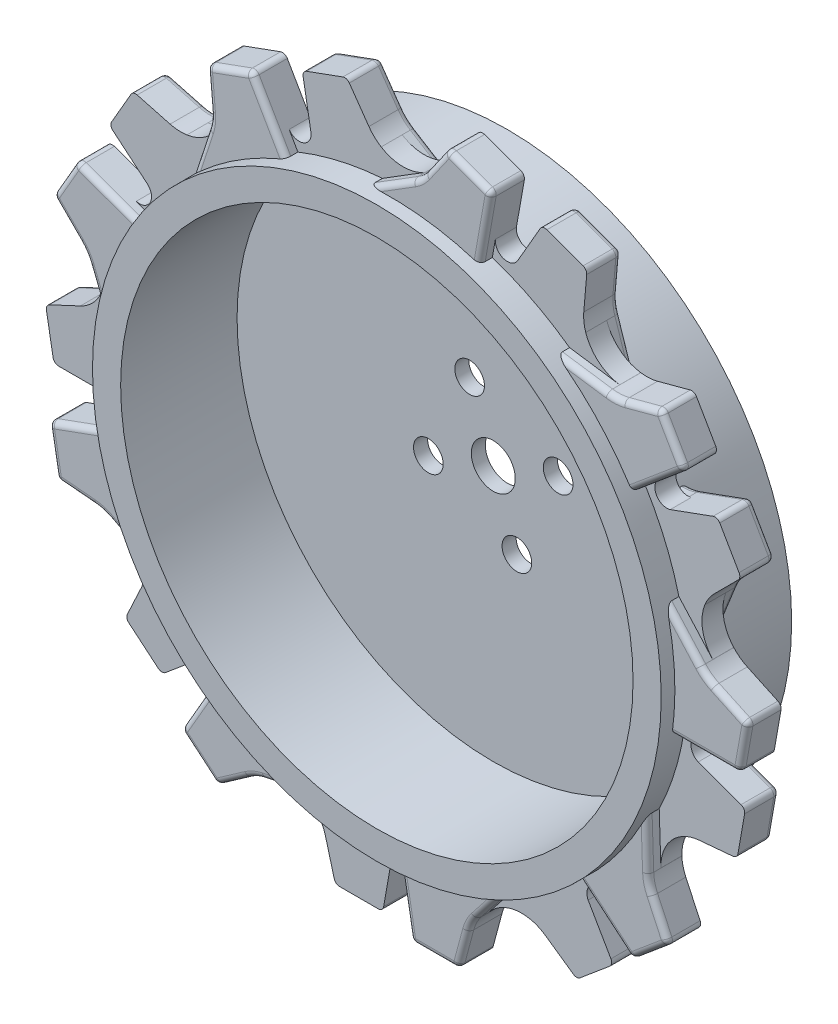
SolidWorks part; units mm, degrees
ref_plane "Front Plane" through (0, 0, 0) normal (0, 0, 1) x (1, 0, 0)
ref_plane "Top Plane" through (0, 0, 0) normal (0, 1, 0) x (1, 0, 0)
ref_plane "Right Plane" through (0, 0, 0) normal (1, 0, 0) x (0, 0, -1)
sketch "Sketch1" plane through (0, 0, 0) normal (0, 0, 1) x (1, 0, 0)
  line L0 (0, 45.1139) -> (0, -45.1139) construction
  line L1 (38.9794, 0) -> (-38.9794, 0) construction
  line L2 (2.4045, 32.578) -> (-2.5355, 35.6448)
  line L3 (-3.9413, 36.9734) -> (-6.1886, 40.1749)
  line L4 (-6.9314, 40.4086) -> (-11.0919, 38.8936)
  line L5 (-11.5032, 38.1809) -> (-10.5355, 32.7)
  line L6 (15.7303, 36.6424) -> (12.9485, 31.8217)
  line L7 (20.6644, 35.4101) -> (16.5034, 36.924)
  line L8 (20.7468, 30.8567) -> (21.0832, 34.7537)
  line L9 (22.7827, 23.4107) -> (20.9697, 28.9353)
  line L10 (35.6034, 17.9585) -> (30.3737, 16.0537)
  line L11 (38.591, 13.8429) -> (36.3766, 17.6772)
  line L12 (35.7273, 10.3018) -> (38.4899, 13.0708)
  line L13 (32.5006, 3.2892) -> (34.663, 8.6867)
  line L14 (38.8173, -9.1284) -> (33.5868, -7.226)
  line L15 (38.4605, -14.2015) -> (39.2288, -9.8409)
  line L16 (33.9906, -15.0734) -> (37.8867, -14.728)
  line L17 (27.0112, -18.3714) -> (32.1371, -15.6266)
  line L18 (23.8682, -31.944) -> (21.0842, -27.1246)
  line L19 (20.3339, -35.601) -> (23.7254, -32.7544)
  line L20 (16.3493, -33.3956) -> (19.556, -35.6354)
  line L21 (8.8829, -31.4357) -> (14.5739, -32.628)
  line L22 (-2.2492, -39.8127) -> (-1.284, -34.3313)
  line L23 (-7.3072, -40.3423) -> (-2.8794, -40.3417)
  line L24 (-8.942, -36.0917) -> (-7.9253, -39.8686)
  line L25 (-13.4018, -29.791) -> (-9.8086, -34.3624)
  line L26 (-27.3141, -29.0526) -> (-23.0513, -25.474)
  line L27 (-31.5291, -26.207) -> (-28.1369, -29.0527)
  line L28 (-30.0492, -21.9) -> (-31.6982, -25.4469)
  line L29 (-29.4157, -14.2067) -> (-29.6015, -20.0183)
  line L30 (-39.5984, -4.6984) -> (-34.0327, -4.6971)
  line L31 (-40.9983, 0.1908) -> (-40.2288, -4.1696)
  line L32 (-37.0961, 2.5389) -> (-40.6392, 0.8818)
  line L33 (-31.6656, 8.0251) -> (-35.5436, 3.6926)
  line L34 (-33.3542, 21.8542) -> (-29.0898, 18.2776)
  line L35 (-31.2838, 26.4994) -> (-33.4973, 22.6645)
  line L36 (-26.7853, 25.7898) -> (-30.5646, 26.7978)
  line L37 (-19.0988, 26.5018) -> (-24.8544, 25.6757)
  arc A0 (-10.559, 30.9131) -> (-19.0988, 26.5018) centre (0, 0) ccw
  arc A1 (-10.559, 30.9131) -> (-10.5355, 32.7) centre (-15.2295, 31.8682) ccw
  arc A2 (-11.5032, 38.1809) -> (-11.0919, 38.8936) centre (-10.873, 38.2922) cw
  arc A3 (-6.9314, 40.4086) -> (-6.1886, 40.1749) centre (-6.7124, 39.8072) cw
  arc A4 (-3.9413, 36.9734) -> (-2.5355, 35.6448) centre (0.012, 39.7484) ccw
  arc A5 (11.7819, 30.468) -> (12.9485, 31.8217) centre (8.818, 34.2018) ccw
  arc A6 (15.7303, 36.6424) -> (16.5034, 36.924) centre (16.2846, 36.3226) cw
  arc A7 (20.6644, 35.4101) -> (21.0832, 34.7537) centre (20.4456, 34.8087) cw
  arc A8 (20.7468, 30.8567) -> (20.9697, 28.9353) centre (25.5589, 30.4413) ccw
  arc A9 (28.6099, 15.7666) -> (30.3737, 16.0537) centre (28.7395, 20.532) ccw
  arc A10 (35.6034, 17.9585) -> (36.3766, 17.6772) centre (35.8224, 17.3572) cw
  arc A11 (38.591, 13.8429) -> (38.4899, 13.0708) centre (38.0368, 13.5229) cw
  arc A12 (35.7273, 10.3018) -> (34.663, 8.6867) centre (39.1466, 6.8905) ccw
  arc A13 (32.051, -6.3122) -> (33.5868, -7.226) centre (35.2134, -2.745) ccw
  arc A14 (38.8173, -9.1284) -> (39.2288, -9.8409) centre (38.5985, -9.7298) cw
  arc A15 (38.4605, -14.2015) -> (37.8867, -14.728) centre (37.8302, -14.0905) cw
  arc A16 (33.9906, -15.0734) -> (32.1371, -15.6266) centre (34.4171, -19.8845) ccw
  arc A17 (20.4951, -25.4374) -> (21.0842, -27.1246) centre (25.2106, -24.7375) ccw
  arc A18 (23.8682, -31.944) -> (23.7254, -32.7544) centre (23.314, -32.2641) cw
  arc A19 (20.3339, -35.601) -> (19.556, -35.6354) centre (19.9224, -35.1107) cw
  arc A20 (16.3493, -33.3956) -> (14.5739, -32.628) centre (13.5835, -37.3553) ccw
  arc A21 (-0.6507, -32.6602) -> (-1.284, -34.3313) centre (3.4114, -35.1551) ccw
  arc A22 (-2.2492, -39.8127) -> (-2.8794, -40.3417) centre (-2.8795, -39.7017) cw
  arc A23 (-7.3072, -40.3423) -> (-7.9253, -39.8686) centre (-7.3073, -39.7023) cw
  arc A24 (-8.942, -36.0917) -> (-9.8086, -34.3624) centre (-13.606, -37.3472) ccw
  arc A25 (-21.492, -24.6009) -> (-23.0513, -25.474) centre (-19.984, -29.1232) ccw
  arc A26 (-27.3141, -29.0526) -> (-28.1369, -29.0527) centre (-27.7256, -28.5624) cw
  arc A27 (-31.5291, -26.207) -> (-31.6982, -25.4469) centre (-31.1178, -25.7167) cw
  arc A28 (-30.0492, -21.9) -> (-29.6015, -20.0183) centre (-34.4291, -19.8638) ccw
  arc A29 (-32.277, -5.0306) -> (-34.0327, -4.6971) centre (-34.0286, -9.4642) ccw
  arc A30 (-39.5984, -4.6984) -> (-40.2288, -4.1696) centre (-39.5986, -4.0584) cw
  arc A31 (-40.9983, 0.1908) -> (-40.6392, 0.8818) centre (-40.368, 0.302) cw
  arc A32 (-37.0961, 2.5389) -> (-35.5436, 3.6926) centre (-39.1424, 6.914) ccw
  arc A33 (-27.9592, 16.8936) -> (-29.0898, 18.2776) centre (-32.1509, 14.6232) ccw
  arc A34 (-33.3542, 21.8542) -> (-33.4973, 22.6645) centre (-32.943, 22.3445) cw
  arc A35 (-31.2838, 26.4994) -> (-30.5646, 26.7978) centre (-30.7296, 26.1794) cw
  arc A36 (-26.7853, 25.7898) -> (-24.8544, 25.6757) centre (-25.5406, 30.4567) ccw
  arc A37 (11.7819, 30.468) -> (2.4045, 32.578) centre (0, 0) ccw
  arc A38 (28.6099, 15.7666) -> (22.7827, 23.4107) centre (0, 0) ccw
  arc A39 (32.051, -6.3122) -> (32.5006, 3.2892) centre (0, 0) ccw
  arc A40 (20.4951, -25.4374) -> (27.0112, -18.3714) centre (0, 0) ccw
  arc A41 (-0.6507, -32.6602) -> (8.8829, -31.4357) centre (0, 0) ccw
  arc A42 (-21.492, -24.6009) -> (-13.4018, -29.791) centre (0, 0) ccw
  arc A43 (-32.277, -5.0306) -> (-29.4157, -14.2067) centre (0, 0) ccw
  arc A44 (-27.9592, 16.8936) -> (-31.6656, 8.0251) centre (0, 0) ccw
  point P0 (2.4045, 32.578)
  point P8 (-3.96, 37)
  point P9 (-6.4704, 40.5764)
  point P10 (-11.5966, 38.7098)
  point P11 (-10.5355, 32.7)
  point P13 (-15.2295, 31.8682)
  point P14 (-2.56, 35.66)
  point P22 (-11.5966, 38.7098)
  point P25 (-6.4704, 40.5764)
  point P28 (-3.3742, 36.1655)
  point P135 (0, 0)
  dimension "D19" = 0.64
  dimension "D20" = 4.83
  dimension "D1" = 2.4045
  dimension "D2" = 32.578
  dimension "D3" = 90.2278
  dimension "D4" = 77.9588
  dimension "D5" = 3.96
  dimension "D6" = 37
  dimension "D7" = 6.4704
  dimension "D8" = 40.5764
  dimension "D9" = 11.5966
  dimension "D10" = 38.7098
  dimension "D11" = 10.5355
  dimension "D12" = 32.7
  dimension "D13" = 2.56
  dimension "D14" = 35.66
  dimension "D15" = 3.3742
  dimension "D16" = 36.1655
  dimension "D17" = 15.2295
  dimension "D18" = 31.8682
  dimension "D21" = 9
extrude "Boss-Extrude3" add sketch "Sketch1" along normal blind 3.9878
sketch "Sketch2" plane through (0, 0, 3.9878) normal (0, 0, 1) x (1, 0, 0)
  circle A0 centre (0, 0) radius 32.675
  dimension "D1" = 65.35
extrude "Boss-Extrude4" add sketch "Sketch2" along normal blind 3.03 and the other way blind 11.96
ref_plane "Plane1" through (0, 0, 1.5718) normal (0, 0, 1) x (1, 0, 0)
sketch "Sketch3" plane through (0, 0, 1.5718) normal (0, 0, 1) x (1, 0, 0)
  line L0 (0, 45) -> (0, -45) construction
  line L1 (-45, 0) -> (45, 0) construction
  line L2 (10.2397, 31.0203) -> (11.5033, 38.181)
  line L3 (11.092, 38.8936) -> (6.9319, 40.4084)
  line L4 (27.7835, 17.181) -> (33.3543, 21.8542)
  line L5 (6.1887, 40.1742) -> (3.9614, 36.9942)
  line L6 (2.5563, 35.6637) -> (-2.4045, 32.578)
  line L7 (33.4973, 22.6644) -> (31.2841, 26.4989)
  line L8 (30.5642, 26.7972) -> (26.814, 25.7928)
  line L9 (24.8825, 25.6768) -> (19.0988, 26.5018)
  line L10 (32.3271, -4.6975) -> (39.5985, -4.6985)
  line L11 (40.2288, -4.1697) -> (40.9982, 0.1903)
  line L12 (40.6385, 0.8815) -> (37.12, 2.5227)
  line L13 (35.5658, 3.6754) -> (31.6656, 8.0251)
  line L14 (21.7445, -24.378) -> (27.3141, -29.0526)
  line L15 (28.1368, -29.0527) -> (31.5287, -26.2073)
  line L16 (31.6975, -25.4466) -> (30.0572, -21.9278)
  line L17 (29.6075, -20.0457) -> (29.4157, -14.2067)
  line L18 (0.9874, -32.6517) -> (2.2491, -39.8127)
  line L19 (2.8793, -40.3417) -> (7.3067, -40.3423)
  line L20 (7.9249, -39.868) -> (8.9302, -36.118)
  line L21 (9.7955, -34.3873) -> (13.4018, -29.791)
  line L22 (-20.2317, -25.6474) -> (-23.8682, -31.944)
  line L23 (-23.7255, -32.7543) -> (-20.3343, -35.6006)
  line L24 (-19.5558, -35.6347) -> (-16.3753, -33.4083)
  line L25 (-14.5999, -32.6386) -> (-8.8829, -31.4357)
  line L26 (-31.9842, -6.6423) -> (-38.8174, -9.1284)
  line L27 (-39.2288, -9.8408) -> (-38.4606, -14.201)
  line L28 (-37.8862, -14.7275) -> (-34.0186, -15.0664)
  line L29 (-32.1639, -15.618) -> (-27.0112, -18.3714)
  line L30 (-28.7709, 15.4707) -> (-35.6034, 17.9586)
  line L31 (-36.3766, 17.6773) -> (-38.5908, 13.8434)
  line L32 (-38.4892, 13.0708) -> (-35.7443, 10.3252)
  line L33 (-34.678, 8.7105) -> (-32.5006, 3.2892)
  line L34 (-12.0954, 30.3449) -> (-15.7302, 36.6425)
  line L35 (-16.5033, 36.924) -> (-20.6639, 35.4103)
  line L36 (-21.0826, 34.7532) -> (-20.7448, 30.8855)
  line L37 (-20.9659, 28.9632) -> (-22.7827, 23.4107)
  arc A0 (33.3543, 21.8542) -> (33.4973, 22.6644) centre (32.943, 22.3445) ccw
  arc A1 (11.5033, 38.181) -> (11.092, 38.8936) centre (10.873, 38.2922) ccw
  arc A2 (6.9319, 40.4084) -> (6.1887, 40.1742) centre (6.7129, 39.807) ccw
  arc A3 (-2.4045, 32.578) -> (-12.0954, 30.3449) centre (0, 0) ccw
  arc A4 (2.5563, 35.6637) -> (3.9614, 36.9942) centre (0.0053, 39.7651) ccw
  arc A5 (31.2841, 26.4989) -> (30.5642, 26.7972) centre (30.7298, 26.179) ccw
  arc A6 (24.8825, 25.6768) -> (26.814, 25.7928) centre (25.5645, 30.4584) ccw
  arc A7 (39.5985, -4.6985) -> (40.2288, -4.1697) centre (39.5985, -4.0585) ccw
  arc A8 (40.9982, 0.1903) -> (40.6385, 0.8815) centre (40.3679, 0.3015) ccw
  arc A9 (35.5658, 3.6754) -> (37.12, 2.5227) centre (39.1619, 6.8999) ccw
  arc A10 (27.3141, -29.0526) -> (28.1368, -29.0527) centre (27.7255, -28.5624) ccw
  arc A11 (31.5287, -26.2073) -> (31.6975, -25.4466) centre (31.1174, -25.717) ccw
  arc A12 (29.6075, -20.0457) -> (30.0572, -21.9278) centre (34.4349, -19.8871) ccw
  arc A13 (2.2491, -39.8127) -> (2.8793, -40.3417) centre (2.8794, -39.7017) ccw
  arc A14 (7.3067, -40.3423) -> (7.9249, -39.868) centre (7.3067, -39.7023) ccw
  arc A15 (9.7955, -34.3873) -> (8.9302, -36.118) centre (13.5955, -37.3687) ccw
  arc A16 (-23.8682, -31.944) -> (-23.7255, -32.7543) centre (-23.314, -32.2641) ccw
  arc A17 (-20.3343, -35.6006) -> (-19.5558, -35.6347) centre (-19.9228, -35.1104) ccw
  arc A18 (-14.5999, -32.6386) -> (-16.3753, -33.4083) centre (-13.6054, -37.3651) ccw
  arc A19 (-38.8174, -9.1284) -> (-39.2288, -9.8408) centre (-38.5985, -9.7298) ccw
  arc A20 (-38.4606, -14.201) -> (-37.8862, -14.7275) centre (-37.8303, -14.09) ccw
  arc A21 (-32.1639, -15.618) -> (-34.0186, -15.0664) centre (-34.4402, -19.878) ccw
  arc A22 (-35.6034, 17.9586) -> (-36.3766, 17.6773) centre (-35.8224, 17.3572) ccw
  arc A23 (-38.5908, 13.8434) -> (-38.4892, 13.0708) centre (-38.0366, 13.5233) ccw
  arc A24 (-34.678, 8.7105) -> (-35.7443, 10.3252) centre (-39.16, 6.9103) ccw
  arc A25 (-15.7302, 36.6425) -> (-16.5033, 36.924) centre (-16.2845, 36.3226) ccw
  arc A26 (-20.6639, 35.4103) -> (-21.0826, 34.7532) centre (-20.4451, 34.8089) ccw
  arc A27 (-20.9659, 28.9632) -> (-20.7448, 30.8855) centre (-25.5565, 30.4652) ccw
  arc A28 (-22.7827, 23.4107) -> (-28.7709, 15.4707) centre (0, 0) ccw
  arc A29 (-32.5006, 3.2892) -> (-31.9842, -6.6423) centre (0, 0) ccw
  arc A30 (-27.0112, -18.3714) -> (-20.2317, -25.6474) centre (0, 0) ccw
  arc A31 (-8.8829, -31.4357) -> (0.9874, -32.6517) centre (0, 0) ccw
  arc A32 (13.4018, -29.791) -> (21.7445, -24.378) centre (0, 0) ccw
  arc A33 (29.4157, -14.2067) -> (32.3271, -4.6975) centre (0, 0) ccw
  arc A34 (31.6656, 8.0251) -> (27.7835, 17.181) centre (0, 0) ccw
  arc A35 (19.0988, 26.5018) -> (10.2397, 31.0203) centre (0, 0) ccw
  point P0 (-2.4045, 32.578)
  point P8 (6.4704, 40.5764)
  point P9 (11.5966, 38.7098)
  point P11 (15.2295, 31.8682)
  point P19 (11.5966, 38.7098)
  point P24 (6.4704, 40.5764)
  point P27 (3.3949, 36.1853)
  point P114 (0, 0)
  dimension "D10" = 0.64
  dimension "D18" = 4.83
  dimension "D1" = 2.4045
  dimension "D2" = 90
  dimension "D3" = 32.578
  dimension "D4" = 3.3949
  dimension "D5" = 36.1853
  dimension "D6" = 6.4704
  dimension "D7" = 11.5966
  dimension "D8" = 10.2397
  dimension "D9" = 15.2295
  dimension "D11" = 6.1887
  dimension "D12" = 40.5764
  dimension "D13" = 38.7098
  dimension "D15" = 31.8682
  dimension "D16" = 40.1742
  dimension "D17" = 6.9319
extrude "Boss-Extrude5" add sketch "Sketch3" along normal blind 3.878
fillet "Fillet1" radius 0.64 135 edges at (0.0836, 34.1256, 5.4498) (3.3262, 36.2579, 5.4498) (5.075, 38.5842, 5.4498) (6.5205, 40.4174, 5.4498) (9.0119, 39.651, 5.4498) (11.4273, 38.6121, 5.4498) (10.8722, 34.6048, 5.4498) (21.8734, 26.1815, 0) (20.7611, 29.8848, 0) (20.915, 32.8052, 0) (20.9851, 35.1529, 0) (12.4324, 31.0934, 0) (14.3394, 34.2321, 0) (16.0656, 36.9239, 0) (30.5721, 19.5203, 5.4498) (33.5732, 22.2333, 5.4498) (21.9995, 26.088, 5.4498) (25.8541, 25.6371, 5.4498) (28.6891, 26.295, 5.4498) (30.9748, 26.7702, 5.4498) (33.5852, 5.9963, 0) (35.1135, 9.5481, 0) (37.1086, 11.6863, 0) (38.6714, 13.4397, 0) (29.5102, 15.8275, 0) (32.9886, 17.0061, 0) (36.0412, 17.9586, 0) (35.967, -4.698, 5.4498) (40.0099, -4.5488, 5.4498) (33.6217, 5.8436, 5.4498) (36.2846, 3.0205, 5.4498) (38.8793, 1.7021, 5.4498) (40.9356, 0.597, 5.4498) (29.5821, -16.9947, 0) (33.0359, -15.2563, 0) (35.9387, -14.9007, 0) (38.2629, -14.5621, 0) (32.7798, -6.8442, 0) (36.202, -8.1772, 0) (39.1527, -9.4097, 0) (24.5325, -26.718, 5.4498) (27.7254, -29.2024, 5.4498) (29.5119, -17.1352, 5.4498) (29.7371, -21.0095, 5.4498) (30.8773, -23.6872, 5.4498) (31.7422, -25.8556, 5.4498) (20.7115, -26.3134, 0) (22.4762, -29.5343, 0) (23.9443, -32.3752, 0) (22.0297, -34.1777, 0) (19.9508, -35.7501, 0) (17.9526, -34.5155, 0) (15.5004, -32.922, 0) (-11.5997, -32.0837, 0) (-9.2879, -35.1832, 0) (-8.4336, -37.9802, 0) (-7.6966, -40.2103, 0) (-1.048, -33.4703, 0) (-1.7666, -37.072, 0) (-2.468, -40.1919, 0) (1.619, -36.2364, 5.4498) (2.468, -40.1919, 5.4498) (11.5931, -32.0962, 5.4498) (9.2753, -35.2089, 5.4498) (8.4276, -37.993, 5.4498) (7.6963, -40.2101, 5.4498) (-22.0521, -28.7994, 5.4498) (-23.9443, -32.3752, 5.4498) (-11.7502, -32.039, 5.4498) (-15.5265, -32.9336, 5.4498) (-17.9655, -34.5215, 5.4498) (-19.9508, -35.7498, 5.4498) (-22.3171, -24.9661, 0) (-25.1827, -27.2633, 0) (-27.7254, -29.2024, 0) (-29.833, -27.6299, 0) (-31.7426, -25.8556, 0) (-30.8737, -23.6734, 0) (-29.7302, -20.9818, 0) (-35.4047, -7.8868, 5.4498) (-39.1528, -9.4097, 5.4498) (-29.5954, -16.9905, 5.4498) (-33.0633, -15.2484, 5.4498) (-35.9524, -14.897, 5.4498) (-38.2628, -14.5618, 5.4498) (-33.6106, 5.8521, 0) (-36.2615, 3.0373, 0) (-38.8676, 1.7103, 0) (-40.9359, 0.5972, 0) (-33.1438, -4.7799, 0) (-36.8155, -4.6978, 0) (-40.0098, -4.5488, 0) (-32.1911, 16.7161, 5.4498) (-36.0412, 17.9586, 5.4498) (-33.5927, 6.0081, 5.4498) (-35.1294, 9.5718, 5.4498) (-37.1167, 11.698, 5.4498) (-38.6711, 13.4399, 5.4498) (-28.4621, 17.6428, 0) (-31.222, 20.0659, 0) (-33.5732, 22.2333, 0) (-32.3905, 24.5819, 0) (-30.9748, 26.7705, 0) (-28.675, 26.2938, 0) (-25.8256, 25.6351, 0) (-21.8715, 26.1955, 5.4498) (-20.7581, 29.9132, 5.4498) (-20.9137, 32.8194, 5.4498) (-20.9848, 35.1528, 5.4498) (-18.5836, 36.1672, 5.4498) (-16.0656, 36.924, 5.4498) (-10.4627, 31.8103, 0) (-11.0193, 35.4405, 0) (-11.4273, 38.6121, 0) (-9.0117, 39.6511, 0) (-6.5203, 40.4177, 0) (-5.0649, 38.5741, 0) (-3.3056, 36.238, 0) (18.5839, 36.1671, 0) (32.3907, 24.5817, 5.4498) (37.4838, 15.7601, 0) (40.6135, -1.9897, 5.4498) (38.8447, -12.0212, 0) (29.8328, -27.63, 5.4498) (11.7372, -32.0337, 0) (-5.0933, -40.342, 0) (5.093, -40.342, 5.4498) (-22.0299, -34.1775, 5.4498) (-29.5089, -17.1215, 0) (-38.8447, -12.0209, 5.4498) (-40.6135, -1.9894, 0) (-37.4837, 15.7603, 5.4498) (-21.9855, 26.0875, 0) (-13.9149, 33.4973, 5.4498) (-0.0732, 34.1162, 0)
fillet "Fillet2" radius 4.83 9 edges at (-29.5062, -17.0381, 2.7798) (-11.6512, -32.0182, 2.7798) (11.6556, -32.0166, 2.7798) (29.5086, -17.0341, 2.7798) (33.5542, 5.9189, 2.7798) (21.8994, 26.1023, 2.7798) (-0.0023, 34.0722, 2.7798) (-21.903, 26.0993, 2.7798) (-33.555, 5.9143, 2.7798)
sketch "Sketch4" plane through (0, 0, 3.9878) normal (0, 0, 1) x (1, 0, 0)
  line L0 (0, 0) -> (0, 42.8482) construction
  line L1 (29.3357, 18.4831) -> (26.8311, 16.9051)
  line L2 (10.5918, 33.0155) -> (9.6875, 30.1967)
  line L3 (28.0565, 14.7825) -> (30.6829, 16.1663)
  line L4 (34.3532, -4.6978) -> (31.4202, -4.2967)
  line L5 (30.9946, -6.7103) -> (33.8959, -7.3385)
  line L6 (23.2964, -25.6805) -> (21.3074, -23.488)
  line L7 (11.9905, 29.3584) -> (13.1129, 32.1067)
  line L8 (19.4299, -25.0633) -> (21.2487, -27.4095)
  line L9 (1.339, -34.647) -> (1.2247, -31.689)
  line L10 (-1.2262, -31.6889) -> (-1.341, -34.6553)
  line L11 (-21.245, -27.4018) -> (-19.4311, -25.0624)
  line L12 (-21.3086, -23.4869) -> (-23.3033, -25.6855)
  line L13 (-33.8881, -7.335) -> (-30.9949, -6.7088)
  line L14 (-31.4204, -4.2951) -> (-34.3617, -4.6972)
  line L15 (-30.6747, 16.1639) -> (-28.0558, 14.7839)
  line L16 (-26.8303, 16.9064) -> (-29.3419, 18.489)
  line L17 (-13.1082, 32.0996) -> (-11.9891, 29.359)
  line L18 (-9.686, 30.1972) -> (-10.5927, 33.024)
  arc A0 (11.9905, 29.3584) -> (9.6875, 30.1967) centre (0, 0) ccw
  arc A1 (10.5918, 33.0155) -> (13.1129, 32.1067) centre (11.9642, 32.8714) ccw
  arc A2 (29.3357, 18.4831) -> (30.6829, 16.1663) centre (30.2944, 17.4905) ccw
  arc A3 (28.0565, 14.7825) -> (26.8311, 16.9051) centre (0, 0) ccw
  arc A4 (34.3532, -4.6978) -> (33.8959, -7.3385) centre (34.4496, -6.0744) ccw
  arc A5 (30.9946, -6.7103) -> (31.4202, -4.2967) centre (0, 0) ccw
  arc A6 (23.2964, -25.6805) -> (21.2487, -27.4095) centre (22.4854, -26.797) ccw
  arc A7 (19.4299, -25.0633) -> (21.3074, -23.488) centre (0, 0) ccw
  arc A8 (1.339, -34.647) -> (-1.341, -34.6553) centre (0, -34.981) ccw
  arc A9 (-1.2262, -31.6889) -> (1.2247, -31.689) centre (0, 0) ccw
  arc A10 (-21.245, -27.4018) -> (-23.3033, -25.6855) centre (-22.4854, -26.797) ccw
  arc A11 (-21.3086, -23.4869) -> (-19.4311, -25.0624) centre (0, 0) ccw
  arc A12 (-33.8881, -7.335) -> (-34.3617, -4.6972) centre (-34.4496, -6.0744) ccw
  arc A13 (-31.4204, -4.2951) -> (-30.9949, -6.7088) centre (0, 0) ccw
  arc A14 (-30.6747, 16.1639) -> (-29.3419, 18.489) centre (-30.2944, 17.4905) ccw
  arc A15 (-26.8303, 16.9064) -> (-28.0558, 14.7839) centre (0, 0) ccw
  arc A16 (-13.1082, 32.0996) -> (-10.5927, 33.024) centre (-11.9642, 32.8714) ccw
  arc A17 (-9.686, 30.1972) -> (-11.9891, 29.359) centre (0, 0) ccw
  point P16 (11.9642, 32.8714)
  point P51 (0, 0)
  dimension "D1" = 1.38
  dimension "D3" = 11.9642
  dimension "D6" = 31.7126
  dimension "D2" = 32.8714
  dimension "D4" = 10.5918
  dimension "D5" = 13.1129
  dimension "D7" = 9.6875
  dimension "D8" = 11.9905
  dimension "D9" = 9
extrude "Boss-Extrude6" add sketch "Sketch4" against normal up to surface (2.416 mm away) up to face at (5.5082, 36.4882, 1.5718)
sketch "Sketch5" plane through (0, 0, 7.0178) normal (0, 0, 1) x (1, 0, 0)
  circle A0 centre (0, 0) radius 29.439
  dimension "D1" = 58.878
extrude "Cut-Extrude1" cut sketch "Sketch5" against normal blind 13.3772
sketch "Sketch7" plane through (0, 0, -7.9722) normal (0, 0, -1) x (-1, 0, 0)
  line L0 (3.4202, 9.3969) -> (-3.4202, -9.3969) construction
  line L1 (-9.3969, 3.4202) -> (9.3969, -3.4202) construction
  line L2 (0, 0) -> (0, 14.6675) construction
  circle A0 centre (0, 0) radius 2.5265
  circle A1 centre (0, 0) radius 7.935 construction
  circle A2 centre (2.7139, 7.4565) radius 1.705
  circle A3 centre (-2.7139, -7.4565) radius 1.705
  circle A4 centre (-7.4565, 2.7139) radius 1.705
  circle A5 centre (7.4565, -2.7139) radius 1.705
  point P7 (0, 0)
  dimension "D1" = 5.053
  dimension "D3" = 15.87
  dimension "D4" = 3.41
  dimension "D2" = 20
  dimension "D5" = 20
extrude "Cut-Extrude2" cut sketch "Sketch7" against normal up to surface (1.6128 mm away) up to face at (29.439, 0, -6.3594)
